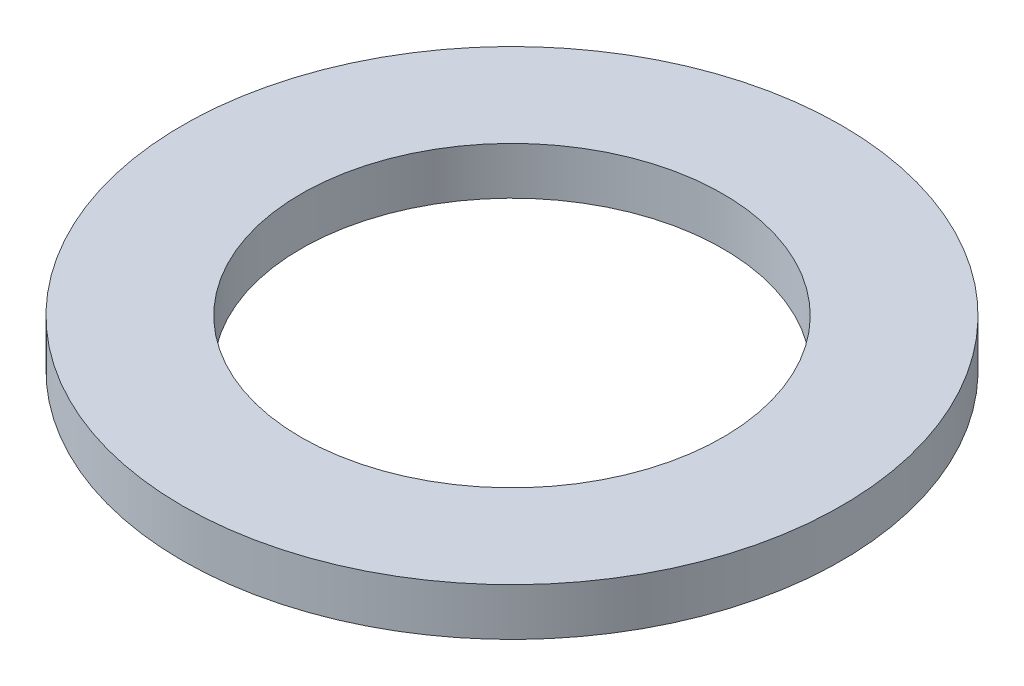
SolidWorks part; units mm, degrees
ref_plane "Front Plane" through (0, 0, 0) normal (0, 0, 1) x (1, 0, 0)
ref_plane "Top Plane" through (0, 0, 0) normal (0, 1, 0) x (1, 0, 0)
ref_plane "Right Plane" through (0, 0, 0) normal (1, 0, 0) x (0, 0, -1)
sketch "Sketch1" plane through (0, 0, 0) normal (0, 1, 0) x (1, 0, 0)
  circle A0 centre (0, 0) radius 62.5
  dimension "FLANGE_OD" = 125
extrude "Boss-Extrude1" add sketch "Sketch1" along normal blind 9
sketch "Sketch2" plane through (0, 0, 0) normal (0, 1, 0) x (1, 0, 0)
  circle A0 centre (0, 0) radius 40
  dimension "BORE_D" = 80
extrude "Cut-Extrude1" cut sketch "Sketch2" along normal through all
sketch "Sketch3" plane through (0, 9, 0) normal (0, 1, 0) x (1, 0, 0)
  circle A0 centre (0, 0) radius 24.9032 construction
  circle A1 centre (-24.9032, 0) radius 1.7844
  dimension "BOLT_D" = 3.5689
  dimension "BOLT_PCD" = 49.8065
extrude "Cut-Extrude2" cut sketch "Sketch3" against normal blind 7.8671 rebuild error yes
pattern_circular "CirPattern1" count 8 over 360 rebuild error yes
